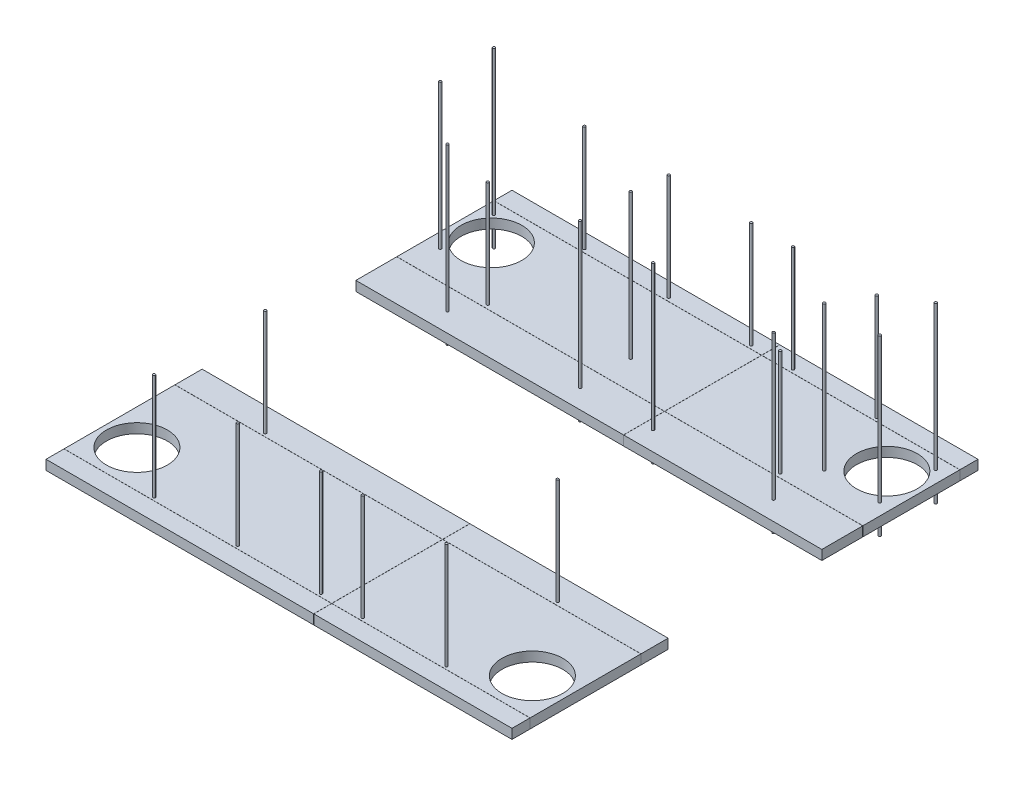
SolidWorks part; units mm, degrees
ref_plane "Front" through (0, 0, 0) normal (0, 0, 1) x (1, 0, 0)
ref_plane "Top" through (0, 0, 0) normal (0, 1, 0) x (1, 0, 0)
ref_plane "Right" through (0, 0, 0) normal (1, 0, 0) x (0, 0, -1)
sketch "Sketch1" plane through (0, 0, 0) normal (0, 1, 0) x (1, 0, 0)
  line L1 (-2454.275, 2454.275) -> (2454.275, 2454.275)
  line L2 (-2454.275, 2454.275) -> (-2454.275, -2454.275)
  line L3 (-2454.275, -2454.275) -> (2454.275, -2454.275)
  line L4 (2454.275, 2454.275) -> (2454.275, -2454.275)
  line L5 (-2454.275, 2454.275) -> (2454.275, -2454.275) construction
  line L6 (-2454.275, -2454.275) -> (2454.275, 2454.275) construction
  point P0 (0, 0)
  dimension "D1" = 4908.55
  dimension "D2" = 4908.55
extrude "Boss-Extrude1" add sketch "Sketch1" along normal blind 101.6
sketch "Sketch2" plane through (0, 101.6, 0) normal (0, 1, 0) x (1, 0, 0)
  line L0 (-2454.275, 2454.275) -> (-2454.275, -2454.275) construction
  line L1 (2454.275, -809.625) -> (-2454.275, -809.625)
  line L2 (2454.275, -809.625) -> (2454.275, 809.625)
  line L3 (2454.275, 809.625) -> (-2454.275, 809.625)
  line L4 (-2454.275, -809.625) -> (-2454.275, 809.625)
  line L5 (2454.275, -809.625) -> (-2454.275, 809.625) construction
  line L6 (2454.275, 809.625) -> (-2454.275, -809.625) construction
  point P0 (0, 0)
  dimension "D1" = 1619.25
extrude "Cut-Extrude1" cut sketch "Sketch2" against normal through all
sketch "Sketch4" plane through (0, 101.6, 0) normal (0, 1, 0) x (1, 0, 0)
  line L0 (-2454.275, -2263.775) -> (2454.275, -2263.775)
  line L3 (-2454.275, -2454.275) -> (2454.275, -2454.275) construction
  line L4 (-2454.275, -1095.375) -> (2454.275, -1095.375)
  line L5 (-2454.275, -809.625) -> (-2454.275, -2454.275) construction
  line L6 (-2454.275, -809.625) -> (2454.275, -809.625) construction
  line L7 (-2454.275, 2263.775) -> (2454.275, 2263.775)
  line L10 (-2454.275, 1241.425) -> (2454.275, 1241.425)
  line L11 (-2454.275, 2454.275) -> (-2454.275, 809.625) construction
  line L12 (2454.275, 809.625) -> (2454.275, 2454.275) construction
  line L13 (2454.275, 2454.275) -> (-2454.275, 2454.275) construction
  line L14 (2454.275, 809.625) -> (-2454.275, 809.625) construction
  line L15 (-2454.275, -1095.375) -> (-2454.275, -2263.775) construction
  line L16 (2454.275, -1095.375) -> (2454.275, -2263.775) construction
  line L17 (2454.275, 1241.425) -> (2454.275, 2263.775) construction
  line L18 (-2454.275, 1241.425) -> (-2454.275, 2263.775) construction
  line L19 (2454.275, -2454.275) -> (2454.275, -809.625) construction
  dimension "D1" = 190.5
  dimension "D2" = 1168.4
  dimension "D3" = 285.75
  dimension "D4" = 190.5
  dimension "D5" = 1022.35
  dimension "D6" = 431.8
extrude "Cut-Extrude-Thin1" cut sketch "Sketch4" against normal through all thin thin type one direction wall 1.27
sketch "Sketch5" plane through (0, 101.6, 0) normal (0, 1, 0) x (1, 0, 0)
  line L0 (365.125, -2454.275) -> (365.125, 2454.275)
  line L1 (-2454.275, -2454.275) -> (2454.275, -2454.275) construction
  line L2 (2454.275, 2454.275) -> (-2454.275, 2454.275) construction
  line L3 (2454.275, -2263.775) -> (2454.275, -1096.645) construction
  line L4 (-2454.275, -1096.645) -> (-2454.275, -2263.775) construction
  dimension "D1" = 2089.15
  dimension "D2" = 2819.4
extrude "Cut-Extrude-Thin2" cut sketch "Sketch5" against normal through all and the other way through all thin thin type one direction wall 1.27
sketch "Sketch3" plane through (0, 101.6, 0) normal (0, 1, 0) x (1, 0, 0)
  line L1 (-2276.475, -2263.775) -> (-1520.6938, -2263.775)
  line L2 (-2276.475, -2263.775) -> (-2276.475, -1507.9938)
  line L3 (-2276.475, -1507.9938) -> (-1520.6938, -1507.9938)
  line L4 (-1520.6938, -2263.775) -> (-1520.6938, -1507.9938)
  line L5 (2276.475, -2263.775) -> (1520.6938, -2263.775)
  line L6 (2276.475, -2263.775) -> (2276.475, -1507.9938)
  line L7 (2276.475, -1507.9938) -> (1520.6938, -1507.9938)
  line L8 (1520.6938, -2263.775) -> (1520.6938, -1507.9938)
  line L9 (-2276.475, 2263.775) -> (-1520.6938, 2263.775)
  line L10 (-2276.475, 2263.775) -> (-2276.475, 1507.9938)
  line L11 (-2276.475, 1507.9938) -> (-1520.6938, 1507.9938)
  line L12 (-1520.6938, 2263.775) -> (-1520.6938, 1507.9938)
  line L13 (2276.475, 2263.775) -> (1520.6938, 2263.775)
  line L14 (2276.475, 2263.775) -> (2276.475, 1507.9938)
  line L15 (2276.475, 1507.9938) -> (1520.6938, 1507.9938)
  line L16 (1520.6938, 2263.775) -> (1520.6938, 1507.9938)
  line L19 (2454.275, -2263.775) -> (2454.275, -1096.645) construction
  line L20 (366.395, -2263.775) -> (2454.275, -2263.775) construction
  line L21 (-2454.275, -2263.775) -> (365.125, -2263.775) construction
  line L22 (-2454.275, -1096.645) -> (-2454.275, -2263.775) construction
  line L23 (366.395, 2263.775) -> (2454.275, 2263.775) construction
  line L24 (2454.275, 1241.425) -> (2454.275, 2262.505) construction
  line L25 (-2454.275, 2262.505) -> (-2454.275, 1241.425) construction
  line L26 (-2454.275, 2263.775) -> (365.125, 2263.775) construction
  dimension "D1" = 177.8
  dimension "D2" = 177.8
  dimension "D3" = 177.8
  dimension "D4" = 177.8
extrude "SQUARE HOLE" [suppressed] cut sketch "Sketch3" against normal through all
sketch "Sketch6" plane through (0, 101.6, 0) normal (0, 1, 0) x (1, 0, 0)
  line L0 (2082.8, 1865.63) -> (2082.8, 2262.505) construction
  line L1 (-2082.8, 1865.63) -> (2082.8, 1865.63) construction
  line L2 (-2082.8, 1865.63) -> (-2082.8, -1868.17) construction
  line L3 (-2082.8, -1868.17) -> (2082.8, -1868.17) construction
  line L4 (2082.8, 1865.63) -> (2082.8, -1868.17) construction
  line L5 (-2082.8, -1868.17) -> (-2082.8, -2265.045) construction
  line L6 (-2454.275, -2265.045) -> (365.125, -2265.045) construction
  line L7 (366.395, 2262.505) -> (2454.275, 2262.505) construction
  line L9 (2454.275, 1241.425) -> (2454.275, 2262.505) construction
  line L11 (-2454.275, -1096.645) -> (-2454.275, -2263.775) construction
  circle A0 centre (2082.8, 1865.63) radius 320.675
  circle A1 centre (-2082.8, 1865.63) radius 320.675
  circle A2 centre (-2082.8, -1868.17) radius 320.675
  circle A3 centre (2082.8, -1868.17) radius 320.675
  dimension "D1" = 641.35
  dimension "D3" = 50.8
  dimension "D4" = 50.8
  dimension "D2" = 76.2
extrude "Cut-Extrude2" cut sketch "Sketch6" against normal through all
sketch "Sketch7" plane through (0, 101.6, 0) normal (0, 1, 0) x (1, 0, 0)
  line L0 (-1539.875, 2301.875) -> (-295.275, 2301.875) construction
  line L1 (-1539.875, 2301.875) -> (-2454.275, 2301.875) construction
  line L2 (-2454.275, 2454.275) -> (-2454.275, 2263.775) construction
  line L3 (365.125, 2454.275) -> (-2454.275, 2454.275) construction
  line L4 (-295.275, 2301.875) -> (365.125, 2301.875) construction
  line L5 (365.125, 2263.775) -> (365.125, 2454.275) construction
  line L6 (1743.075, 1546.225) -> (1743.075, 1012.825) construction
  line L7 (365.125, 2301.875) -> (974.725, 2301.875) construction
  line L8 (974.725, 2301.875) -> (1743.075, 2301.875) construction
  line L9 (1743.075, 2301.875) -> (2454.275, 2301.875) construction
  line L10 (2454.275, 2263.775) -> (2454.275, 2454.275) construction
  line L11 (366.395, 2263.775) -> (366.395, 2454.275) construction
  line L12 (2454.275, 1546.225) -> (-2454.275, 1546.225) construction
  line L13 (2454.275, 1241.425) -> (2454.275, 2262.505) construction
  line L14 (-2454.275, 2262.505) -> (-2454.275, 1241.425) construction
  line L15 (1743.075, 2301.875) -> (1743.075, 1546.225) construction
  line L16 (-2454.275, 1241.425) -> (365.125, 1241.425) construction
  line L17 (-295.275, 2301.875) -> (-295.275, 1546.225) construction
  line L18 (974.725, 2301.875) -> (974.725, 1546.225) construction
  line L19 (-2454.275, 2136.775) -> (2454.275, 2136.775) construction
  line L20 (-2454.275, 2263.775) -> (365.125, 2263.775) construction
  line L21 (-1539.875, 2301.875) -> (-1539.875, 2136.775) construction
  line L22 (-2454.275, 1012.825) -> (2454.275, 1012.825) construction
  line L23 (-2454.275, 1240.155) -> (-2454.275, 809.625) construction
  line L24 (2454.275, 809.625) -> (2454.275, 1240.155) construction
  line L25 (365.125, 809.625) -> (-2454.275, 809.625) construction
  line L26 (-1692.275, 1012.825) -> (-1692.275, 1546.225) construction
  line L27 (-295.275, 1546.225) -> (-295.275, 1012.825) construction
  line L28 (-2107.4102, -2022.1425) -> (-2107.4102, -819.4758) construction
  line L29 (-1539.875, 1285.875) -> (1539.875, 1285.875) construction
  circle A0 centre (-1539.875, 2301.875) radius 12.7
  circle A4 centre (1743.075, 1546.225) radius 12.7
  circle A5 centre (-1692.275, 1546.225) radius 12.7 construction
  circle A6 centre (473.075, 1012.825) radius 12.7
  circle A7 centre (-295.275, 1546.225) radius 12.7
  circle A8 centre (974.725, 1546.225) radius 12.7 construction
  circle A9 centre (-295.275, 2136.775) radius 12.7 construction
  circle A10 centre (-1539.875, 2136.775) radius 12.7 construction
  circle A11 centre (974.725, 2136.775) radius 12.7 construction
  circle A12 centre (1743.075, 2136.775) radius 12.7 construction
  circle A13 centre (-295.275, 1012.825) radius 12.7
  circle A14 centre (-1692.275, 1012.825) radius 12.7
  circle A15 centre (1743.075, 1012.825) radius 12.7
  circle A16 centre (-2301.875, 1546.225) radius 12.7
  circle A17 centre (2327.275, 1546.225) radius 12.7
  circle A18 centre (-2327.275, 2136.775) radius 12.7
  circle A19 centre (2327.275, 2136.775) radius 12.7
  circle A20 centre (219.075, 2301.875) radius 12.7
  circle A21 centre (658.495, 2301.875) radius 12.7
  circle A22 centre (1539.875, 2301.875) radius 12.7
  circle A23 centre (-650.875, 2301.875) radius 12.7
  circle A24 centre (-1539.875, 1285.875) radius 12.7
  circle A25 centre (1539.875, 1285.875) radius 12.7
  circle A26 centre (-1539.875, -1058.596) radius 12.7
  circle A27 centre (-1539.875, -2230.2499) radius 12.7
  circle A28 centre (-658.766, -2230.2499) radius 12.7
  circle A29 centre (219.075, -2230.2499) radius 12.7
  circle A30 centre (658.495, -2230.2499) radius 12.7
  circle A31 centre (1539.875, -2230.2499) radius 12.7
  circle A32 centre (1539.875, -1058.596) radius 12.7
  dimension "D1" = 25.4
  dimension "D5" = 609.6
  dimension "D7" = 304.8
  dimension "D11" = 127
  dimension "D14" = 152.4
  dimension "D19" = 889
  dimension "D20" = 914.4
  dimension "D21" = 1168.4
  dimension "D2" = 152.4
  dimension "D3" = 914.4
  dimension "D4" = 660.4
  dimension "D6" = 711.2
  dimension "D8" = 762
  dimension "D9" = 127
  dimension "D10" = 127
  dimension "D12" = 203.2
  dimension "D13" = 1981.2
  dimension "D15" = 127
  dimension "D16" = 146.05
  dimension "D17" = 292.1
  dimension "D18" = 914.4
  dimension "D22" = 3079.75
extrude "STUD LAYOUT SKETCH" add sketch "Sketch7" along normal blind 1524 and the other way blind 304.8 separate body
sketch "Sketch8" plane through (0, 1625.6, 0) normal (0, 1, 0) x (1, 0, 0)
  line L1 (-2748.8936, 3759.21) -> (2748.8936, 3759.21)
  line L2 (-2748.8936, 3759.21) -> (-2748.8936, -3759.21)
  line L3 (-2748.8936, -3759.21) -> (2748.8936, -3759.21)
  line L4 (2748.8936, 3759.21) -> (2748.8936, -3759.21)
  line L5 (-2748.8936, 3759.21) -> (2748.8936, -3759.21) construction
  line L6 (-2748.8936, -3759.21) -> (2748.8936, 3759.21) construction
  point P0 (0, 0)
  dimension "D1" = 7518.42
  dimension "D2" = 5497.7872
sketch "Sketch9" plane through (0, -203.2, 0) normal (0, -1, 0) x (1, 0, 0)
  line L1 (2592.4344, 3685.246) -> (-2592.4344, 3685.246)
  line L2 (2592.4344, 3685.246) -> (2592.4344, -3685.246)
  line L3 (2592.4344, -3685.246) -> (-2592.4344, -3685.246)
  line L4 (-2592.4344, 3685.246) -> (-2592.4344, -3685.246)
  line L5 (2592.4344, 3685.246) -> (-2592.4344, -3685.246) construction
  line L6 (2592.4344, -3685.246) -> (-2592.4344, 3685.246) construction
  point P0 (0, 0)
  dimension "D1" = 7370.492
  dimension "D2" = 5184.8688
extrude "Cut-Extrude5" cut sketch "Sketch8" against normal blind 406.4
extrude "Cut-Extrude6" cut sketch "Sketch9" against normal blind 254
